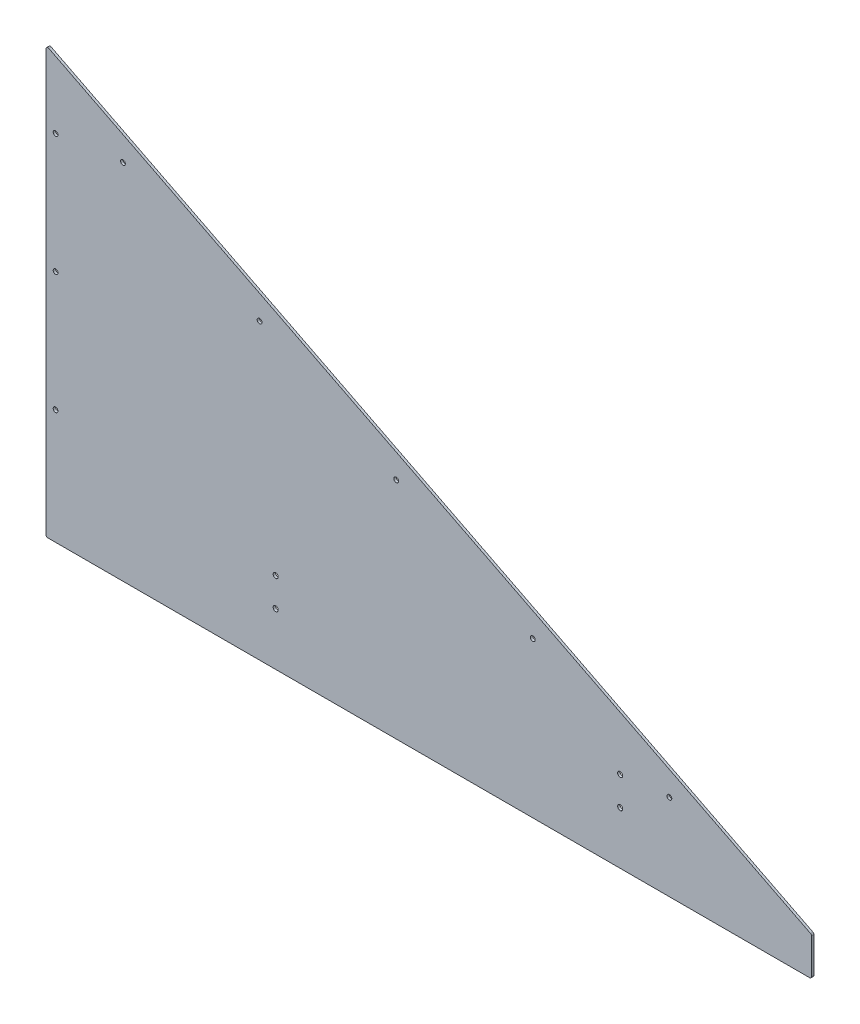
SolidWorks part; units mm, degrees
material "PC High Viscosity"
ref_plane "Front Plane" through (0, 0, 0) normal (0, 0, 1) x (1, 0, 0)
ref_plane "Top Plane" through (0, 0, 0) normal (0, 1, 0) x (1, 0, 0)
ref_plane "Right Plane" through (0, 0, 0) normal (1, 0, 0) x (0, 0, -1)
sketch "Sketch1" plane through (0, 0, 0) normal (0, 0, 1) x (1, 0, 0)
  line L0 (-1016, 514.35) -> (-1016, -50.8)
  line L1 (-1016, -50.8) -> (0, -50.8)
  line L2 (0, -50.8) -> (0, 0)
  line L3 (0, 0) -> (-1016, 514.35)
  point P2 (-1003.3, 419.1)
  point P5 (-1003.3, 260.35)
  point P6 (-1003.3, 101.6)
  point P7 (-711.2, 57.15)
  point P8 (-711.2, 19.05)
  point P11 (-254, 57.15)
  point P13 (-254, 19.05)
  dimension "D1" = 565.15
  dimension "D2" = 1016
  dimension "D3" = 50.8
  dimension "D4" = 12.7
  dimension "D5" = 95.25
  dimension "D6" = 158.75
  dimension "D7" = 158.75
  dimension "D8" = 457.2
  dimension "D9" = 304.8
  dimension "D10" = 38.1
  dimension "D11" = 69.85
extrude "Boss-Extrude1" add sketch "Sketch1" along normal blind 3.175
hole_wizard "1/4 (0.25) Diameter Hole1" positions "Sketch3" profile "Sketch4" hole size "1/4" standard "ANSI Inch" end condition through all
sketch "Sketch3" plane through (0, 0, 3.175) normal (0, 0, 1) x (1, 0, 0)
  point P0 (-1003.3, 419.1)
  point P3 (-1003.3, 260.35)
  point P6 (-1003.3, 101.6)
sketch "Sketch4" plane through (-1003.3, 419.1, 3.175) normal (1, 0, 0) x (0, -1, 0)
  line L0 (0, 0) -> (0, 3.175)
  line L1 (0, 3.175) -> (3.175, 3.175)
  line L2 (3.175, 3.175) -> (3.175, 0)
  line L5 (3.175, 0) -> (0, 0)
  line L11 (0, -6.35) -> (0, 107.95) construction
  dimension "Thru Hole Dia." = 6.35
  dimension "Thru Hole Depth" = 3.175
sketch "Sketch5" plane through (0, 0, 3.175) normal (0, 0, 1) x (1, 0, 0)
  line L0 (-1016, 514.35) -> (-1016, -50.8) construction
  line L1 (0, -50.8) -> (0, 0) construction
  line L2 (-1016, -50.8) -> (0, -50.8) construction
  point P0 (-787.4, -38.1)
  point P1 (-787.4, -25.4)
  point P2 (-508, -25.4)
  point P3 (-508, -38.1)
  point P4 (-228.6, -25.4)
  point P5 (-228.6, -38.1)
  dimension "D1" = 228.6
  dimension "D2" = 228.6
  dimension "D3" = 279.4
  dimension "D4" = 12.7
  dimension "D5" = 25.4
hole_wizard "17/64 (0.26563) Diameter Hole1" positions "Sketch7" profile "Sketch8" hole size "17/64" standard "ANSI Inch" end condition through all
sketch "Sketch7" plane through (0, 0, 3.175) normal (0, 0, 1) x (1, 0, 0)
  point P3 (-254, 19.05)
  point P6 (-711.2, 57.15)
  point P9 (-711.2, 19.05)
  point P13 (-254, 57.15)
sketch "Sketch8" plane through (-254, 19.05, 3.175) normal (1, 0, 0) x (0, -1, 0)
  line L0 (0, 0) -> (0, 3.175)
  line L1 (0, 3.175) -> (3.3735, 3.175)
  line L2 (3.3735, 3.175) -> (3.3735, 0)
  line L5 (3.3735, 0) -> (0, 0)
  line L11 (0, -6.35) -> (0, 107.95) construction
  dimension "Thru Hole Dia." = 6.747
  dimension "Thru Hole Depth" = 3.175
fillet "Fillet1" radius 2.54 4 edges at (0, 0, 1.5875) (0, -50.8, 1.5875) (-1016, -50.8, 1.5875) (-1016, 514.35, 1.5875)
sketch "Sketch9" plane through (0, 0, 3.175) normal (0, 0, 1) x (1, 0, 0)
  line L0 (-913.8659, 430.6165) -> (-188.6975, 63.5) construction
  line L1 (-1.3928, 0.7051) -> (-1012.3128, 512.4833) construction
  line L2 (-1013.46, -50.8) -> (-2.54, -50.8) construction
  point P3 (-551.2817, 247.0583)
  point P5 (-732.5738, 338.8374)
  point P6 (-369.9896, 155.2791)
  dimension "D1" = 28.575
  dimension "D2" = 812.8
  dimension "D3" = 114.3
  dimension "D4" = 203.2
  dimension "D5" = 203.2
hole_wizard "1/4 (0.25) Diameter Hole2" positions "Sketch10" profile "Sketch11" hole size "1/4" standard "ANSI Inch" end condition up to next
sketch "Sketch10" plane through (0, 0, 3.175) normal (0, 0, 1) x (1, 0, 0)
  point P0 (-913.8659, 430.6165)
  point P3 (-732.5738, 338.8374)
  point P12 (-188.6975, 63.5)
  point P15 (-369.9896, 155.2791)
  point P18 (-551.2817, 247.0583)
sketch "Sketch11" plane through (-913.8659, 430.6165, 3.175) normal (1, 0, 0) x (0, -1, 0)
  line L0 (0, 0) -> (0, 3.175)
  line L1 (0, 3.175) -> (3.175, 3.175)
  line L2 (3.175, 3.175) -> (3.175, 0)
  line L5 (3.175, 0) -> (0, 0)
  line L11 (0, -6.35) -> (0, 107.95) construction
  dimension "Thru Hole Dia." = 6.35
  dimension "Thru Hole Depth" = 3.175
equation "\"D4@Sketch9\"=\"D2@Sketch9\"/4"
equation "\"D5@Sketch9\"=\"D2@Sketch9\"/4"
